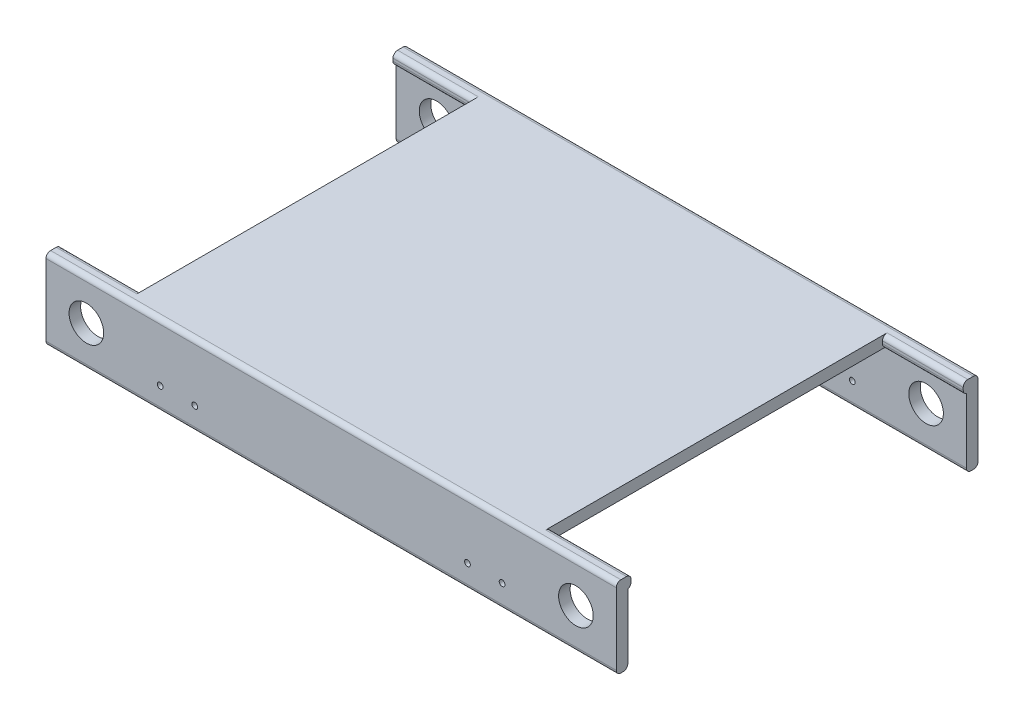
SolidWorks part; units mm, degrees
material "AISI 316 Stainless Steel Sheet (SS)"
ref_plane "Front Plane" through (0, 0, 0) normal (0, 0, 1) x (1, 0, 0)
ref_plane "Top Plane" through (0, 0, 0) normal (0, 1, 0) x (1, 0, 0)
ref_plane "Right Plane" through (0, 0, 0) normal (1, 0, 0) x (0, 0, -1)
sketch "Sketch1" plane through (0, 0, 0) normal (0, 1, 0) x (1, 0, 0)
  line L0 (-78.486, 49.784) -> (-78.486, 45.72)
  line L1 (-78.486, 45.72) -> (-56.261, 45.72)
  line L2 (-56.261, 45.72) -> (-56.261, -45.72)
  line L3 (-56.261, -45.72) -> (-78.486, -45.72)
  line L4 (-78.486, -45.72) -> (-78.486, -49.784)
  line L5 (-78.486, -49.784) -> (78.486, -49.784)
  line L6 (78.486, -49.784) -> (78.486, -45.72)
  line L7 (78.486, -45.72) -> (56.261, -45.72)
  line L8 (56.261, -45.72) -> (56.261, 45.72)
  line L9 (56.261, 45.72) -> (78.486, 45.72)
  line L10 (78.486, 45.72) -> (78.486, 49.784)
  line L11 (78.486, 49.784) -> (-78.486, 49.784)
  line L12 (0, 49.784) -> (0, -49.784) construction
  point P15 (0, 0)
  dimension "D1" = 156.972
  dimension "D2" = 4.064
  dimension "D3" = 4.064
  dimension "D4" = 99.568
  dimension "D5" = 22.225
  dimension "D6" = 22.225
extrude "Boss-Extrude1" add sketch "Sketch1" along normal blind 3.175 contours L2 L3 L4 L5 L6 L7 L8 L9 L10 L11 L0 L1
sketch "Sketch2" plane through (0, 0, 49.784) normal (0, 0, 1) x (1, 0, 0)
  line L0 (-78.486, 3.175) -> (-78.486, -19.05) construction
  line L1 (-78.486, -19.05) -> (-56.261, -19.05) construction
  line L2 (-56.261, -19.05) -> (-56.261, 3.175) construction
  line L3 (-78.486, 3.175) -> (78.486, 3.175) construction
  line L4 (-56.261, 3.175) -> (-78.486, 3.175) construction
  line L5 (0, -12.2237) -> (0, 12.2237) construction
  line L6 (-78.486, 3.175) -> (-78.486, -19.05)
  line L12 (78.486, 3.175) -> (78.486, -19.05)
  line L14 (-78.486, 3.175) -> (78.486, 3.175)
  line L15 (78.486, -19.05) -> (-78.486, -19.05)
  line L16 (-78.486, 3.175) -> (-56.261, -19.05) construction
  line L19 (-78.486, -12.7) -> (78.486, -12.7) construction
  circle A0 centre (-67.3735, -7.9375) radius 4.7625
  circle A1 centre (67.3735, -7.9375) radius 4.7625
  circle A2 centre (-47.0535, -12.7) radius 0.7937
  circle A3 centre (-37.5285, -12.7) radius 0.7937
  circle A4 centre (37.5285, -12.7) radius 0.7937
  circle A5 centre (47.0535, -12.7) radius 0.7937
  dimension "D3" = 9.525
  dimension "D4" = 1.5875
  dimension "D5" = 1.5875
  dimension "D1" = 22.225
  dimension "D2" = 22.225
  dimension "D6" = 9.525
  dimension "D7" = 20.32
  dimension "D8" = 6.35
extrude "Boss-Extrude2" add sketch "Sketch2" against normal blind 3.175
mirror "Mirror2" about plane through (0, 0, 0) normal (0, 0, 1) of "Boss-Extrude2"
fillet "Fillet2" radius 1.27 14 edges at (-67.3735, 0, 45.72) (-67.3735, 0, -45.72) (67.3735, 0, -45.72) (67.3735, 0, 45.72) (67.3735, 3.175, 45.72) (67.3735, 3.175, -45.72) (0, -19.05, -46.609) (0, -19.05, 46.609) (-67.3735, 3.175, -45.72) (-67.3735, 3.175, 45.72) (0, -19.05, -49.784) (0, -19.05, 49.784) (0, 3.175, 49.784) (0, 3.175, -49.784)
